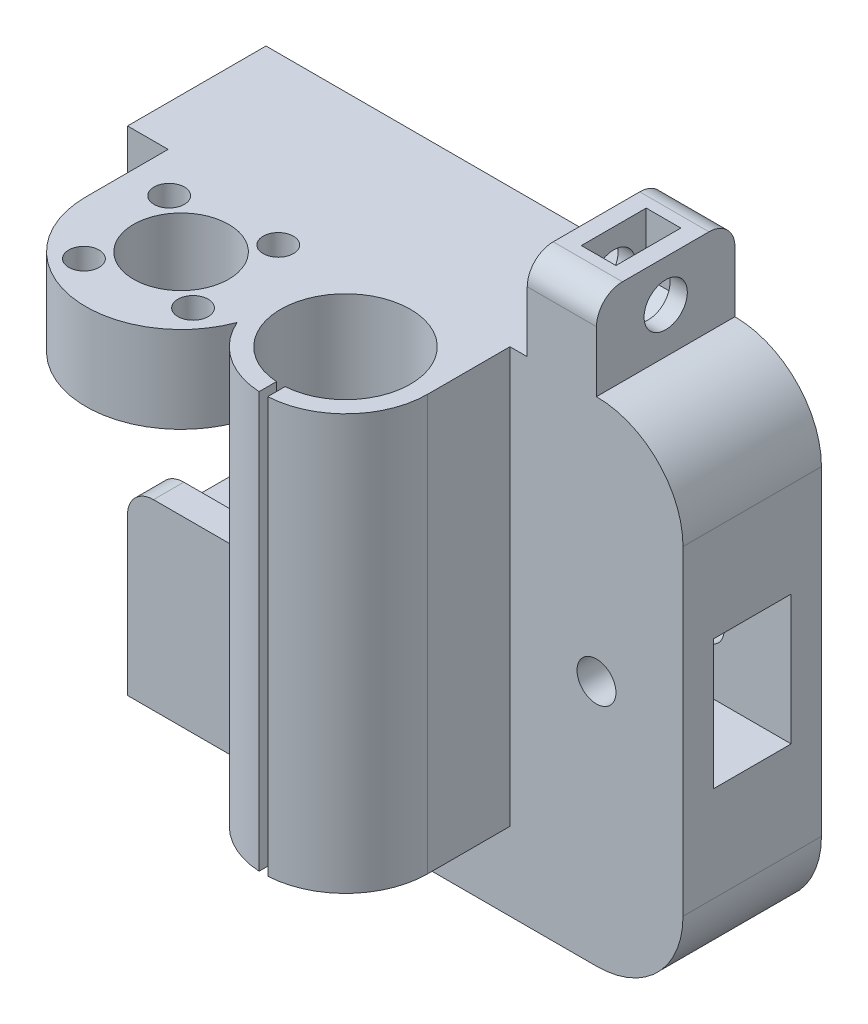
SolidWorks part; units mm, degrees
ref_plane "Front Plane" through (0, 0, 0) normal (0, 0, 1) x (1, 0, 0)
ref_plane "Top Plane" through (0, 0, 0) normal (0, 1, 0) x (1, 0, 0)
ref_plane "Right Plane" through (0, 0, 0) normal (1, 0, 0) x (0, 0, -1)
sketch "Sketch1" plane through (0, 0, 0) normal (0, 1, 0) x (1, 0, 0)
  line L0 (0, 0) -> (64.191, 0)
  line L1 (64.191, 0) -> (64.191, -16)
  line L2 (34.191, -32.9833) -> (34.191, -34.9868)
  line L3 (0, 0) -> (0, -16)
  line L4 (15.691, -25.5) -> (34.691, -25.5) construction
  line L5 (15.691, -25.5) -> (15.691, 0) construction
  line L6 (15.691, -25.5) -> (15.691, -33.5) construction
  line L7 (10.7657, -31.8041) -> (20.6163, -19.1959) construction
  line L8 (9.3869, -20.5747) -> (21.9951, -30.4253) construction
  line L9 (35.191, -32.9833) -> (35.191, -34.9868)
  line L10 (34.691, -25.5) -> (34.691, -32.9833) construction
  line L11 (34.191, -32.9833) -> (35.191, -32.9833) construction
  line L12 (34.191, -34.9868) -> (35.191, -34.9868) construction
  line L13 (64.191, -16) -> (44.191, -16)
  line L14 (44.191, -16) -> (44.191, -25.5)
  line L15 (0, -16) -> (4.691, -16)
  line L16 (4.691, -16) -> (4.691, -25.5)
  circle A0 centre (15.691, -25.5) radius 5.5
  arc A1 (35.191, -32.9833) -> (34.191, -32.9833) centre (34.691, -25.5) ccw
  arc A2 (35.191, -34.9868) -> (44.191, -25.5) centre (34.691, -25.5) ccw
  circle A3 centre (15.691, -25.5) radius 8 construction
  circle A4 centre (10.7657, -31.8041) radius 1.75
  circle A5 centre (9.3869, -20.5747) radius 1.75
  circle A6 centre (20.6163, -19.1959) radius 1.75
  circle A7 centre (21.9951, -30.4253) radius 1.75
  arc A8 (4.691, -25.5) -> (26.0002, -29.3367) centre (15.691, -25.5) ccw
  arc A9 (26.0002, -29.3367) -> (34.191, -34.9868) centre (34.691, -25.5) ccw
  dimension "D1" = 19
  dimension "D2" = 15
  dimension "D3" = 11
  dimension "D5" = 2
  dimension "D6" = 16
  dimension "D7" = 38
  dimension "D8" = 3.5
  dimension "D9" = 22
  dimension "D10" = 1
  dimension "D4" = 25.5
  dimension "D11" = 16
  dimension "D12" = 20
  dimension "D13" = 4.691
extrude "Boss-Extrude1" add sketch "Sketch1" along normal mid plane 57 contours A8 A2 L0 | A2 A8 A0 A4 A5 A6 A7 | A8 A2 L2 A1 L9 | A2 A8 region at (29.3649, 0, 12.581)
sketch "Sketch2" plane through (0, 0, 16) normal (0, 0, 1) x (1, 0, 0)
  line L0 (4.691, 28.5) -> (4.691, -28.5) construction
  line L1 (4.691, 18.5) -> (26.0002, 18.5)
  line L2 (4.691, 18.5) -> (4.691, -28.5)
  line L3 (4.691, -28.5) -> (44.191, -28.5)
  line L5 (26.0002, 28.5) -> (4.691, 28.5) construction
  line L6 (26.0002, 18.5) -> (26.0002, -19.5)
  line L7 (26.0002, -19.5) -> (44.191, -19.5)
  line L8 (44.191, 28.5) -> (44.191, -28.5) construction
  line L9 (44.191, -19.5) -> (44.191, -28.5)
  dimension "D1" = 10
  dimension "D2" = 9
  dimension "D3" = 21.3092
extrude "Cut-Extrude1" cut sketch "Sketch2" along normal through all
sketch "Sketch3" plane through (0, 0, 0) normal (-1, 0, 0) x (0, 0, 1)
  line L0 (8, 28.5) -> (8, 12.5) construction
  line L1 (3.5, 12.5) -> (12.5, 12.5)
  line L2 (3.5, 12.5) -> (3.5, -12.5)
  line L3 (3.5, -12.5) -> (12.5, -12.5)
  line L4 (12.5, 12.5) -> (12.5, -12.5)
  line L5 (0, 28.5) -> (16, 28.5) construction
  line L6 (0, 0) -> (3.5, 0) construction
  line L7 (0, 28.5) -> (0, -28.5) construction
  line L8 (0, -28.5) -> (16, -28.5) construction
  dimension "D1" = 3.5
  dimension "D2" = 16
  dimension "D3" = 25
extrude "Cut-Extrude2" cut sketch "Sketch3" against normal blind 28
sketch "Sketch4" plane through (0, 0, 0) normal (-1, 0, 0) x (0, 0, 1)
  line L0 (16, 28.5) -> (16, -28.5) construction
  line L1 (0, 7.4) -> (16, 7.4)
  line L2 (0, 7.4) -> (0, -7.4)
  line L3 (0, -7.4) -> (16, -7.4)
  line L4 (16, 7.4) -> (16, -7.4)
  point P4 (0, 0)
  point P9 (8, 7.4)
  dimension "D1" = 14.8
extrude "Cut-Extrude3" cut sketch "Sketch4" against normal up to surface (26.0002 mm away) up to face at (26.0002, -0.5, 22.6683)
hole_wizard "M4 Clearance Hole1" positions "3DSketch1" profile "Sketch5" hole size "M4" standard "ANSI Metric" end condition through all
sketch3d "3DSketch1"
  line L0 (54.191, 0, 16) -> (64.191, 0, 16) construction
  line L6 (64.191, 28.5, 16) -> (64.191, -28.5, 16) construction
  point P0 (54.191, 0, 16)
  dimension "D1" = 10
sketch "Sketch5" plane through (54.191, 0, 16) normal (1, 0, 0) x (0, -1, 0)
  line L0 (0, 0) -> (0, 16)
  line L1 (0, 16) -> (2.25, 16)
  line L2 (2.25, 16) -> (2.25, 0)
  line L5 (2.25, 0) -> (0, 0)
  line L11 (0, -6.35) -> (0, 107.95) construction
  dimension "Thru Hole Dia." = 4.5
  dimension "Thru Hole Depth" = 16
sketch "Sketch6" plane through (0, 0, 0) normal (-1, 0, 0) x (0, 0, 1)
  line L0 (8, -22.5) -> (8, 22.5) construction
  line L1 (8, 22.5) -> (8, 28.5) construction
  line L2 (8, -22.5) -> (8, -28.5) construction
  line L3 (0, -28.5) -> (16, -28.5) construction
  line L4 (0, 28.5) -> (16, 28.5) construction
  circle A0 centre (8, 22.5) radius 4.1
  circle A1 centre (8, -22.5) radius 4.1
  dimension "D1" = 45
  dimension "D2" = 8.2
extrude "Cut-Extrude4" cut sketch "Sketch6" against normal blind 30 contours A1 | A0 | A0 region at (0, 22.5, 8) region at (0, -22.5, 8)
sketch "Sketch7" plane through (28, 0, 0) normal (-1, 0, 0) x (0, 0, 1)
  line L0 (0, 0) -> (3.5, 0) construction
  line L1 (3.5, 7.5) -> (12.5, 7.5)
  line L2 (3.5, 7.5) -> (3.5, -7.5)
  line L3 (3.5, -7.5) -> (12.5, -7.5)
  line L4 (12.5, 7.5) -> (12.5, -7.5)
  line L5 (8, 7.5) -> (8, 12.5) construction
  line L6 (12.5, 12.5) -> (3.5, 12.5) construction
  line L7 (12.5, -12.5) -> (12.5, 12.5) construction
  dimension "D1" = 15
extrude "Cut-Extrude5" cut sketch "Sketch7" against normal through all
fillet "Fillet1" radius 10 2 edges at (64.191, 28.5, 8) (64.191, -28.5, 8)
fillet "Fillet2" radius 3 4 edges at (0, -7.4, 14.25) (0, -7.4, 1.75) (0, 7.4, 14.25) (0, 7.4, 1.75)
sketch "Sketch11" plane through (0, 28.5, 0) normal (0, 1, 0) x (1, 0, 0)
  line L0 (0, 0) -> (54.191, 0) construction
  line L1 (46.191, 0) -> (54.191, 0)
  line L2 (46.191, 0) -> (46.191, -16)
  line L3 (46.191, -16) -> (54.191, -16)
  line L4 (54.191, 0) -> (54.191, -16)
  line L5 (54.191, -16) -> (44.191, -16) construction
  point P8 (54.191, -16)
  point P9 (54.191, -16)
  dimension "D1" = 8
extrude "Boss-Extrude2" add sketch "Sketch11" along normal blind 10
sketch "Sketch12" plane through (54.191, 0, 0) normal (1, 0, 0) x (0, 0, -1)
  line L0 (-8, 33.7) -> (-8, 28.5) construction
  line L1 (-16, 28.5) -> (0, 28.5) construction
  line L2 (-11.75, 35.8651) -> (-11.75, 38.5)
  line L3 (-8, 38.0301) -> (-11.75, 35.8651)
  line L4 (-11.75, 35.8651) -> (-11.75, 31.5349)
  line L5 (-11.75, 31.5349) -> (-8, 29.3699)
  line L6 (-8, 29.3699) -> (-4.25, 31.5349)
  line L7 (-4.25, 31.5349) -> (-4.25, 35.8651)
  line L8 (-4.25, 35.8651) -> (-8, 38.0301)
  line L9 (-11.75, 38.5) -> (-4.25, 38.5)
  line L10 (-4.25, 38.5) -> (-4.25, 35.8651)
  circle A0 centre (-8, 33.7) radius 2.5
  circle A1 centre (-8, 33.7) radius 3.75 construction
  line M9 (0, 38.5) -> (-16, 38.5)
  dimension "D1" = 5.2
  dimension "D2" = 5
  dimension "D3" = 7.5
  dimension "D4" = 10
extrude "Cut-Extrude6" cut sketch "Sketch12" against normal blind 4 from offset 2 contours L10 L2 L3 L8 M9 | L7 L8 L3 L4 L5 L6 A0 region at (54.191, 37.1825, 11.6705) region at (54.191, 36.8484, 9.8177) offset against normal yes
sketch "Sketch13" plane through (54.191, 0, 0) normal (1, 0, 0) x (0, 0, -1)
  circle A0 centre (-8, 33.7) radius 2.5 construction
  circle A1 centre (-8, 33.7) radius 2.5
extrude "Cut-Extrude7" cut sketch "Sketch13" against normal through all
fillet "Fillet3" radius 3 2 edges at (50.191, 38.5, 0) (50.191, 38.5, 16)
